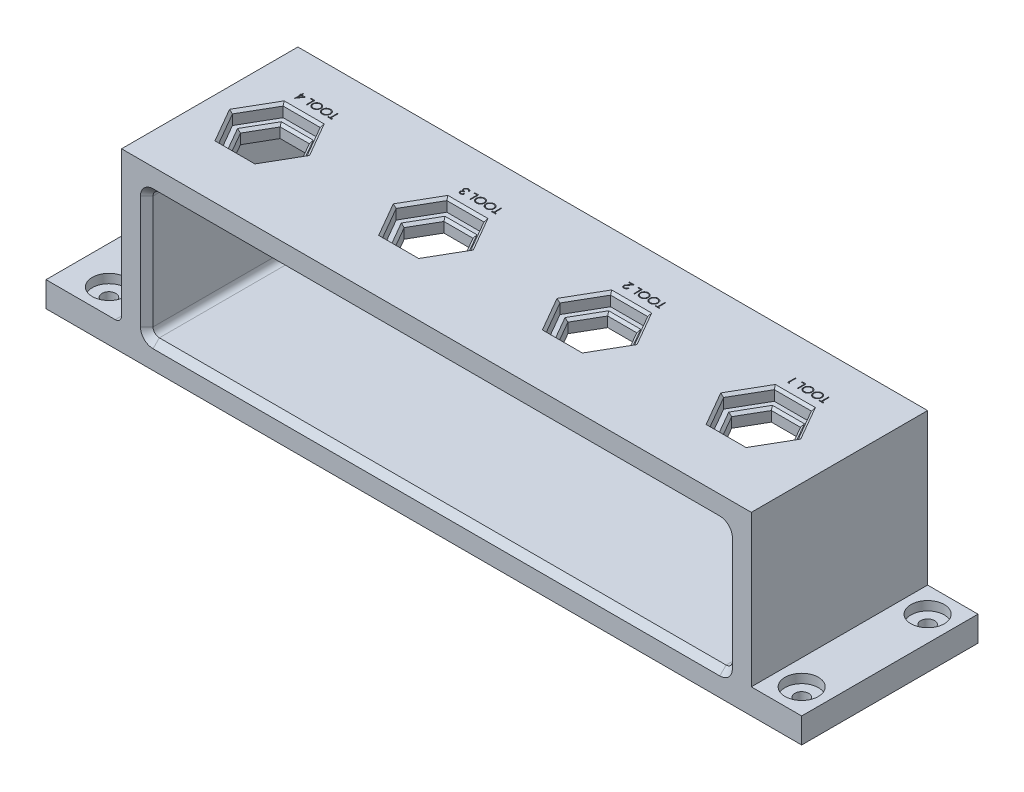
SolidWorks part; units mm, degrees
other "Markup1"
sketch "Sketch1" plane through (0, 0, 0) normal (0.5774, 0.5773, 0.5774) x (0.7071, 0, -0.7071)
sketch "Sketch2" plane through (0, 0, 0) normal (0.5774, 0.5773, 0.5774) x (0.7071, 0, -0.7071)
ref_plane "Front (z)" through (0, 0, 0) normal (0, 0, 1) x (1, 0, 0)
ref_plane "Top (y)" through (0, 0, 0) normal (0, 1, 0) x (1, 0, 0)
ref_plane "Right (x)" through (0, 0, 0) normal (1, 0, 0) x (0, 0, -1)
sketch "Sketch3" plane through (0, 0, 0) normal (0, 1, 0) x (1, 0, 0)
  line L1 (150, -35) -> (-150, -35)
  line L2 (150, -35) -> (150, 35)
  line L3 (150, 35) -> (-150, 35)
  line L4 (-150, -35) -> (-150, 35)
  line L5 (150, -35) -> (-150, 35) construction
  line L6 (150, 35) -> (-150, -35) construction
  point P0 (0, 0)
  dimension "D1" = 70
  dimension "D2" = 300
extrude "Boss-Extrude1" add sketch "Sketch3" along normal blind 10
hole_wizard "CBORE for M5 Hex Head Bolt1" positions "Sketch4" profile "Sketch5" counterbore size "M5" standard "ANSI Metric"
sketch "Sketch4" plane through (0, 10, 0) normal (0, 1, 0) x (1, 0, 0)
  line L0 (150, 35) -> (-150, 35) construction
  line L1 (-150, 35) -> (-150, -35) construction
  point P0 (-135, 25)
  dimension "D1" = 10
  dimension "D2" = 15
sketch "Sketch5" plane through (-135, 10, -25) normal (1, 0, 0) x (0, 0, 1)
  line L0 (0, 0) -> (0, 11.6524)
  line L1 (0, 11.6524) -> (2.75, 10)
  line L2 (2.75, 10) -> (2.75, 3.58)
  line L3 (2.75, 3.58) -> (6.62, 3.58)
  line L4 (6.62, 3.58) -> (6.62, 0)
  line L5 (6.62, 0) -> (0, 0)
  line L10 (0, 11.6524) -> (-2.75, 10) construction
  line L11 (0, -6.35) -> (0, 107.95) construction
  dimension "Hole Dia." = 5.5
  dimension "Hole Depth" = 10
  dimension "C'Bore Dia." = 13.24
  dimension "C'Bore Depth" = 3.58
  dimension "Drill Angle" = 118
pattern_linear "LPattern1" count 2 spacing 275 along (1, 0, 0) count 2 spacing 50 along (0, 0, 1) of "CBORE for M5 Hex Head Bolt1"
sketch "Sketch6" plane through (0, 10, 0) normal (0, 1, 0) x (1, 0, 0)
  line L4 (-120, 35) -> (-120, -35)
  line L7 (150, -35) -> (150, 35) construction
  line L8 (150, 35) -> (-150, 35) construction
  line L9 (-150, -35) -> (150, -35) construction
  line L10 (-150, 35) -> (-150, -35) construction
  line L13 (130, 35) -> (130, -35)
  line L15 (130, 35) -> (-120, 35)
  line L16 (-120, -35) -> (130, -35)
  point P0 (0, 0)
  dimension "D1" = 70
  dimension "D2" = 30
  dimension "D3" = 20
extrude "Boss-Extrude2" add sketch "Sketch6" along normal blind 60
sketch "Sketch7" plane through (0, 0, -35) normal (0, 0, -1) x (-1, 0, 0)
  line L0 (-130, 70) -> (-130, 10) construction
  line L1 (-120, 60) -> (110, 60)
  line L2 (-120, 60) -> (-120, 10)
  line L3 (-120, 10) -> (110, 10)
  line L4 (110, 60) -> (110, 10)
  line L5 (-120, 60) -> (110, 10) construction
  line L6 (-120, 10) -> (110, 60) construction
  line L8 (-150, 10) -> (-130, 10) construction
  line L10 (120, 70) -> (120, 10) construction
  line L11 (-130, 70) -> (120, 70) construction
  point P0 (-5, 35)
  point P9 (-130, 40)
  dimension "D1" = 10
  dimension "D2" = 10
  dimension "D3" = 10
extrude "Cut-Extrude1" cut sketch "Sketch7" along direction (0, 0, 1) on the side against the normal through all
sketch "Sketch8" plane through (0, 70, 0) normal (0, 1, 0) x (1, 0, 0)
  line L1 (-45.9724, 0) -> (-38.6112, -12.75)
  line L2 (-38.6112, -12.75) -> (-23.8888, -12.75)
  line L3 (-23.8888, -12.75) -> (-16.5276, 0)
  line L4 (-16.5276, 0) -> (-23.8888, 12.75)
  line L5 (-23.8888, 12.75) -> (-38.6112, 12.75)
  line L6 (-38.6112, 12.75) -> (-45.9724, 0)
  circle A1 centre (-31.25, 0) radius 12.75 construction
  dimension "D1" = 25.5
  dimension "D2" = 31.25
  dimension "D3" = 12.75
extrude "Cut-Extrude2" cut sketch "Sketch8" against normal offset from surface (5 mm away) 5 up to face at (5, 60, 0)
sketch "Sketch9" plane through (0, 65, 0) normal (0, 1, 0) x (1, 0, 0)
  line L1 (-42.797, 0) -> (-37.0235, -10)
  line L2 (-37.0235, -10) -> (-25.4765, -10)
  line L3 (-25.4765, -10) -> (-19.703, 0)
  line L4 (-19.703, 0) -> (-25.4765, 10)
  line L5 (-25.4765, 10) -> (-37.0235, 10)
  line L6 (-37.0235, 10) -> (-42.797, 0)
  circle A0 centre (-31.25, 0) radius 10 construction
  dimension "D1" = 20
  dimension "D2" = 31.25
  dimension "D3" = 10
extrude "Cut-Extrude3" cut sketch "Sketch9" against normal up to next
chamfer "Chamfer3" distance 1 angle 45 12 edges at (-31.25, 65, 10) (-22.5897, 65, 5) (-22.5897, 65, -5) (-31.25, 65, -10) (-39.9103, 65, 5) (-39.9103, 65, -5) (-42.2918, 70, -6.375) (-42.2918, 70, 6.375) (-31.25, 70, 12.75) (-20.2082, 70, 6.375) (-20.2082, 70, -6.375) (-31.25, 70, -12.75)
pattern_linear "LPattern2" count 2 spacing 65 along (-1, 0, 0) count 3 spacing 65 along (1, 0, 0) of "Cut-Extrude3", "Cut-Extrude2", "Chamfer3" pattern seed only yes
fillet "Fillet1" radius 2.5 5 edges at (120, 10, 0) (-120, 10, 0) (-110, 10, 0) (120, 60, 0) (-110, 60, 0)
chamfer "Chamfer2" distance 2.5 angle 45 16 edges at (-109.2678, 10.7322, 35) (5, 10, 35) (-109.2678, 10.7322, -35) (5, 10, -35) (-110, 35, 35) (-109.2678, 59.2678, 35) (5, 60, 35) (120, 35, 35) (-110, 35, -35) (-109.2678, 59.2678, -35) (5, 60, -35) (120, 35, -35) (119.2678, 59.2678, 35) (119.2678, 10.7322, 35) (119.2678, 59.2678, -35) (119.2678, 10.7322, -35)
sketch "Sketch10" plane through (0, 70, 0) normal (0, 1, 0) x (1, 0, 0)
  line L0 (106.6886, 20) -> (90.8114, 20) construction
  line L1 (130, 35) -> (-120, 35) construction
  line L3 (41.6886, 20) -> (25.8114, 20) construction
  line L4 (-23.3114, 20) -> (-39.1886, 20) construction
  line L5 (-88.3114, 20) -> (-104.1886, 20) construction
  text T0 "TOOL 1"
  text T1 "TOOL 2"
  text T2 "TOOL 3"
  text T3 "TOOL 4"
  dimension "D1" = 15
extrude "Cut-Extrude4" cut sketch "Sketch10" against normal blind 1
sketch "Sketch11" plane through (0, 10, 0) normal (0, 1, 0) x (1, 0, 0)
  line L0 (-120, 35) -> (-115, 35)
  line L1 (-122.5, 35) -> (-150, 35) construction
  line L2 (-120, 35) -> (-120, -35)
  line L3 (-150, -35) -> (-122.5, -35) construction
  line L4 (-115, 35) -> (-115, -35)
  line L5 (-115, -35) -> (-120, -35)
  line L8 (-150, 35) -> (-150, -35) construction
  dimension "D1" = 30
